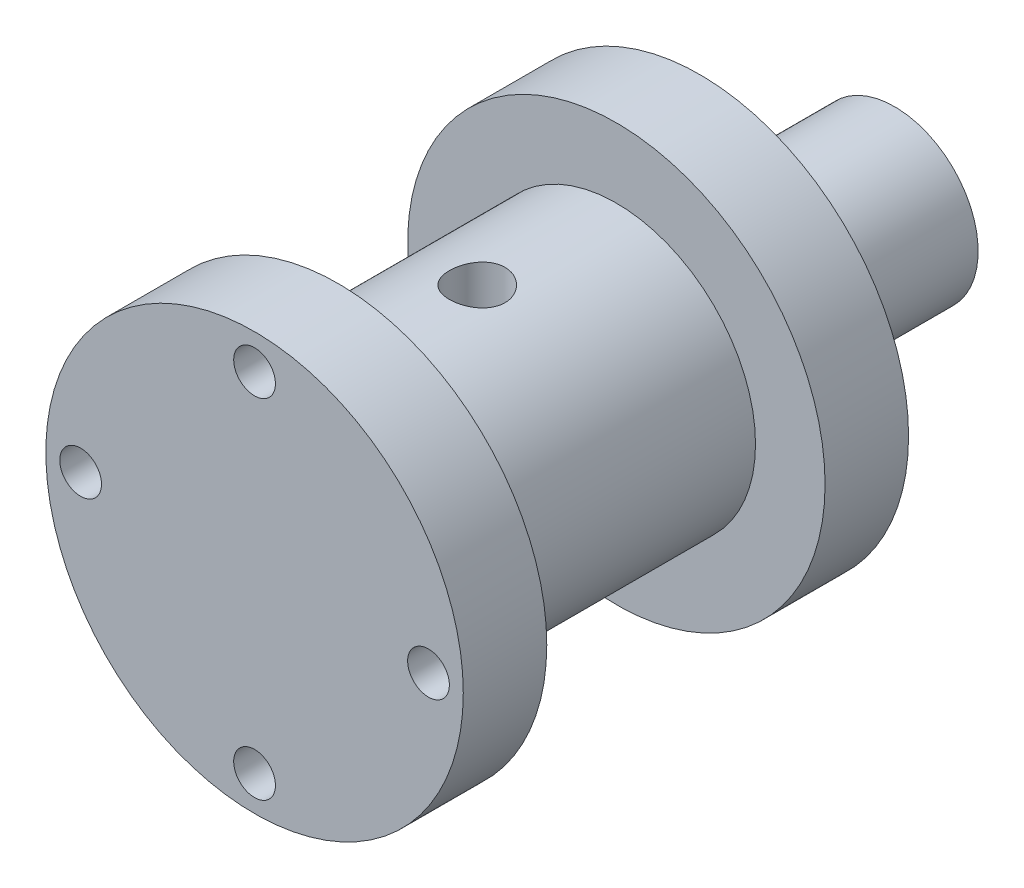
SolidWorks part; units mm, degrees
ref_plane "Front Plane" through (0, 0, 0) normal (0, 0, 1) x (1, 0, 0)
ref_plane "Top Plane" through (0, 0, 0) normal (0, 1, 0) x (1, 0, 0)
ref_plane "Right Plane" through (0, 0, 0) normal (1, 0, 0) x (0, 0, -1)
sketch "Sketch1" plane through (0, 0, 0) normal (0, 0, 1) x (1, 0, 0)
  circle A0 centre (0, 0) radius 5
  dimension "D1" = 10
extrude "Boss-Extrude1" add sketch "Sketch1" along normal blind 5 and the other way blind 5
sketch "Sketch3" plane through (0, 0, 5) normal (0, 0, 1) x (1, 0, 0)
  circle A0 centre (0, 0) radius 7.5
  dimension "D1" = 15
extrude "Boss-Extrude2" add sketch "Sketch3" along normal blind 3
mirror "Mirror1" about plane through (0, 0, 0) normal (0, 0, 1) of "Boss-Extrude2"
ref_plane "Plane1" through (0, 5, 0) normal (0, 1, 0) x (1, 0, 0)
sketch "Sketch4" plane through (0, 5, 0) normal (0, 1, 0) x (1, 0, 0)
  circle A0 centre (0, 0) radius 1
  dimension "D1" = 2
extrude "Cut-Extrude1" cut sketch "Sketch4" against normal through all contours A0
sketch "Sketch5" plane through (0, 0, 5) normal (0, 0, -1) x (-1, 0, 0)
  line L1 (0, 8.25) -> (0, -8.25) construction
  circle A0 centre (0, 6.25) radius 0.75
  circle A1 centre (0, 0) radius 7.5 construction
  dimension "D1" = 1.5
  dimension "D2" = 6.25
extrude "Cut-Extrude2" cut sketch "Sketch5" against normal through all
pattern_circular "CirPattern1" count 4 over 360 about axis through (0, 0, -5) along (0, 0, 1) of "Cut-Extrude2" reverse direction yes
sketch "Sketch6" plane through (0, 0, -8) normal (0, 0, -1) x (-1, 0, 0)
  circle A0 centre (0, 0) radius 3
  dimension "D1" = 6
extrude "Boss-Extrude3" add sketch "Sketch6" along normal blind 7
